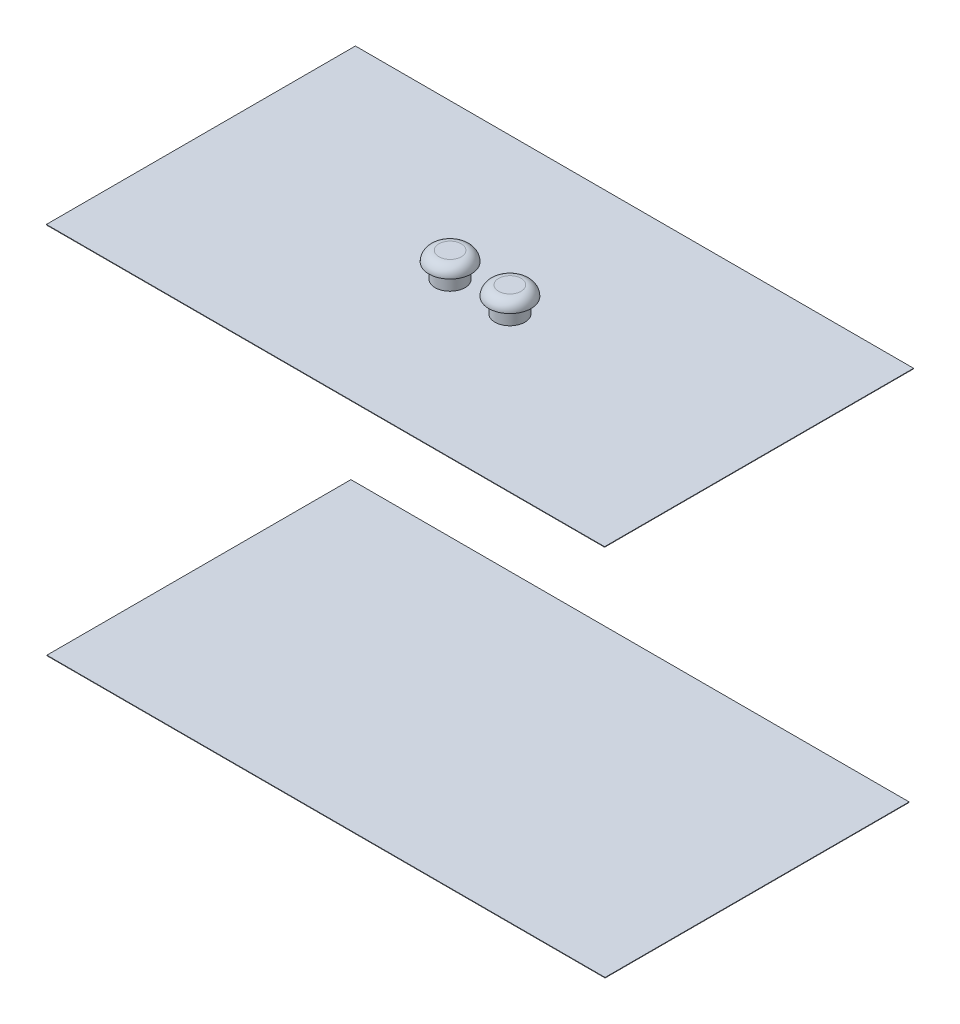
SolidWorks part; units mm, degrees
ref_plane "Front Plane" through (0, 0, 0) normal (0, 0, 1) x (1, 0, 0)
ref_plane "Top Plane" through (0, 0, 0) normal (0, 1, 0) x (1, 0, 0)
ref_plane "Right Plane" through (0, 0, 0) normal (1, 0, 0) x (0, 0, -1)
sketch "Sketch2" plane through (0, -375, 0) normal (0, -1, 0) x (1, 0, 0)
  line L0 (-569.2929, -611) -> (569.2929, -611) construction
  line L1 (-560, -1) -> (560, -1)
  line L2 (-560, -1) -> (-560, -611)
  line L3 (-560, -611) -> (560, -611)
  line L4 (560, -1) -> (560, -611)
  line L5 (560, 170) -> (560, -620) construction
base flange "Base-Flange1" sketch "Sketch2" thickness 1 reverse thickness direction no parameters "D1"=0.8
sketch "Sketch8" plane through (0, 375, 0) normal (0, 1, 0) x (1, 0, 0)
  line L1 (0, 0) -> (-560, 0)
  line L2 (0, 0) -> (0, 620)
  line L3 (0, 620) -> (-560, 620)
  line L4 (-560, 0) -> (-560, 620)
base flange "Base-Flange2" sketch "Sketch8" thickness 1 reverse thickness direction no parameters "D1"=0.8
sketch "Sketch11" plane through (0, 375, 0) normal (0, 1, 0) x (1, 0, 0)
  line L1 (0, 0) -> (560, 0)
  line L2 (0, 0) -> (0, 620)
  line L3 (0, 620) -> (560, 620)
  line L4 (560, 0) -> (560, 620)
base flange "Base-Flange3" sketch "Sketch11" thickness 1 reverse thickness direction no parameters "D1"=0.8
sketch "Sketch14" plane through (0, 375, 0) normal (0, 1, 0) x (1, 0, 0)
  circle A0 centre (-60, 310) radius 30
  circle A1 centre (60, 310) radius 30
  dimension "D1" = 60
  dimension "D2" = 60
extrude "Boss-Extrude1" add sketch "Sketch14" along normal blind 30
sketch "Sketch17" plane through (0, 405, 0) normal (0, 1, 0) x (1, 0, 0)
  circle A0 centre (-60, 310) radius 42.5
  circle A1 centre (60, 310) radius 42.5
  dimension "D1" = 85
  dimension "D2" = 85
extrude "Boss-Extrude2" add sketch "Sketch17" along normal blind 20
fillet "Fillet1" radius 20 2 edges at (-60, 425, -267.5) (60, 425, -267.5)
sketch "Bend-Lines1" [suppressed] plane through (0, 0, 0) normal (0, 1, 0) x (1, 0, 0)
sketch "Bounding-Box1" [suppressed] plane through (0, 0, 0) normal (0, 1, 0) x (1, 0, 0)
sheet metal parameters "Sheet-Metal1" thickness 1 parameters "D1"=0.8
flat pattern "Flat-Pattern1" [suppressed]
sketch "Bend-Lines2" plane through (0, 0, 0) normal (0, 1, 0) x (1, 0, 0)
sketch3d "Bounding-Box2" [suppressed]
  line L0 (-560, 611, 0) -> (560, 611, 0) construction
  line L1 (-560, 1, 0) -> (560, 1, 0) construction
  line L2 (-560, 611, 0) -> (-560, 1, 0) construction
  line L3 (560, 611, 0) -> (560, 1, 0) construction
sheet metal parameters "Sheet-Metal2" thickness 1 parameters "D1"=0.8
flat pattern "Flat-Pattern2"
sketch "Bend-Lines3" plane through (0, 0, 0) normal (0, 1, 0) x (1, 0, 0)
sketch3d "Bounding-Box3" [suppressed]
  line L0 (-560, 620, 0) -> (-560, 0, 0) construction
  line L1 (0, 620, 0) -> (0, 0, 0) construction
  line L2 (-560, 620, 0) -> (0, 620, 0) construction
  line L3 (-560, 0, 0) -> (0, 0, 0) construction
sheet metal parameters "Sheet-Metal3" thickness 1 parameters "D1"=0.8
flat pattern "Flat-Pattern3"
sketch "Bend-Lines4" plane through (0, 0, 0) normal (0, 1, 0) x (1, 0, 0)
sketch "Bounding-Box4" [suppressed] plane through (0, 0, 0) normal (0, 1, 0) x (1, 0, 0)
sheet metal parameters "Sheet-Metal4" thickness 1 parameters "D1"=0.8
flat pattern "Flat-Pattern4"
sketch "Bend-Lines5" plane through (0, 0, 0) normal (0, 1, 0) x (1, 0, 0)
sketch3d "Bounding-Box5" [suppressed]
  line L0 (560, 0, 0) -> (-560, 0, 0) construction
  line L1 (560, 620, 0) -> (-560, 620, 0) construction
  line L2 (560, 0, 0) -> (560, 620, 0) construction
  line L3 (-560, 0, 0) -> (-560, 620, 0) construction
sheet metal parameters "Sheet-Metal5" thickness 1 parameters "D1"=0.8
flat pattern "Flat-Pattern4"
sketch "Bend-Lines5" plane through (0, 0, 0) normal (0, 1, 0) x (1, 0, 0)
sketch3d "Bounding-Box5" [suppressed]
  line L0 (560, 0, 0) -> (-560, 0, 0) construction
  line L1 (560, 620, 0) -> (-560, 620, 0) construction
  line L2 (560, 0, 0) -> (560, 620, 0) construction
  line L3 (-560, 0, 0) -> (-560, 620, 0) construction
